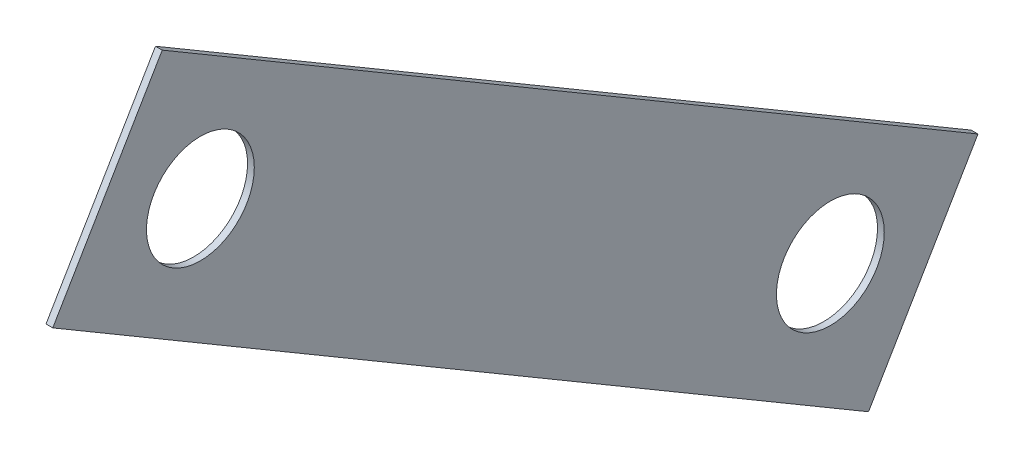
SolidWorks part; units mm, degrees
material "6063-O"
ref_plane "Front" through (0, 0, 0) normal (0, 0, 1) x (1, 0, 0)
ref_plane "Top" through (0, 0, 0) normal (0, 1, 0) x (1, 0, 0)
ref_plane "Right" through (0, 0, 0) normal (1, 0, 0) x (0, 0, -1)
sketch "Sketch1" plane through (0, 0, 0) normal (1, 0, 0) x (0, 0, -1)
  line L0 (-217.9306, 69.4128) -> (166.3647, -156.9544)
  line L1 (-217.9306, 69.4128) -> (-166.3647, 156.9544)
  line L2 (166.3647, -156.9544) -> (217.9306, -69.4128)
  line L3 (-166.3647, 156.9544) -> (217.9306, -69.4128)
  line L4 (-217.9306, 69.4128) -> (217.9306, -69.4128) construction
  line L5 (166.3647, -156.9544) -> (-166.3647, 156.9544) construction
  line L6 (-206.9161, 0) -> (49793.0839, 0) construction
  line L7 (-192.1476, 113.1836) -> (192.1476, -113.1836) construction
  circle A0 centre (-148.3768, 87.4006) radius 25.4
  circle A1 centre (148.3768, -87.4006) radius 25.4
  point P1 (0, 0)
  point P3 (0, 0)
  dimension "D4" = 50.8
  dimension "D1" = 446.01
  dimension "D2" = 30.5
  dimension "D3" = 101.6
  dimension "D5" = 50.8
  dimension "D6" = 50.8
extrude "Boss-Extrude1" add sketch "Sketch1" along normal blind 3.175
